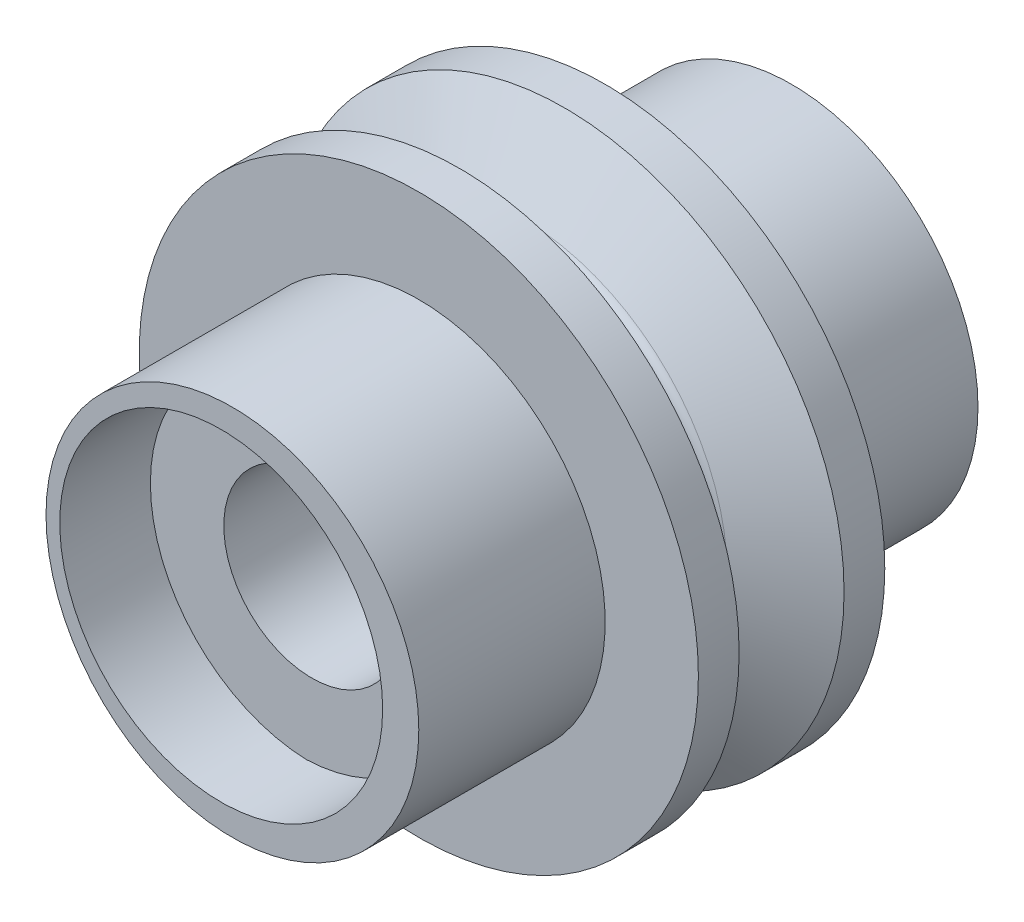
SolidWorks part; units mm, degrees
material "Nylon 101"
ref_plane "Front Plane" through (0, 0, 0) normal (0, 0, 1) x (1, 0, 0)
ref_plane "Top Plane" through (0, 0, 0) normal (0, 1, 0) x (1, 0, 0)
ref_plane "Right Plane" through (0, 0, 0) normal (1, 0, 0) x (0, 0, -1)
sketch "Sketch1" plane through (0, 0, 0) normal (0, 0, 1) x (1, 0, 0)
  circle A0 centre (0, 0) radius 12.7
  circle A1 centre (-0.762, 0) radius 11
  dimension "D1" = 0.762
  dimension "D2" = 22
  dimension "D3" = 25.4
extrude "Boss-Extrude1" add sketch "Sketch1" along normal blind 12.7
ref_axis "Axis1" through (-0.762, 0, 12.7) along (0, 0, -1)
sketch "Sketch2" plane through (0, 0, 0) normal (1, 0, 0) x (0, 0, -1)
  line L0 (-7.2875, 11) -> (-7.2875, 6)
  line L1 (0, 11) -> (-12.7, 11) construction
  line L2 (-7.2875, 6) -> (6.35, 6)
  line L3 (6.35, 6) -> (6.35, 13.62)
  line L4 (5.6901, 14.001) -> (2.775, 19.05)
  line L5 (2.775, 19.05) -> (0, 19.05)
  line L6 (0, 19.05) -> (0, 11)
  line L7 (0, -12.7) -> (0, 12.7) construction
  line L8 (0, 11) -> (-7.2875, 11)
  line L9 (-12.7, 12.7) -> (-12.7, -12.7) construction
  line L10 (-12.7, 0) -> (0, 0) construction
  line L11 (0, 0) -> (16.8777, 0) construction
  arc A0 (6.35, 13.62) -> (5.6901, 14.001) centre (6.35, 14.382) cw
  point P17 (0, 12.7)
  point P18 (0, 12.7)
  point P19 (0, 0)
  point P20 (0, 12.7)
  point P21 (0, 18.5789)
  point P25 (2.3973, 19.05)
  dimension "D1" = 5.4125
  dimension "D3" = 0.762
  dimension "D2" = 6
  dimension "D4" = 6.35
  dimension "D5" = 19.05
  dimension "D6" = 7.62
  dimension "D7" = 60
revolve "Revolve1" add sketch "Sketch2" angle 360 about L11
mirror "Mirror1" about plane through (0, 6, -6.35) normal (0, 0, 1) of bodies 102
